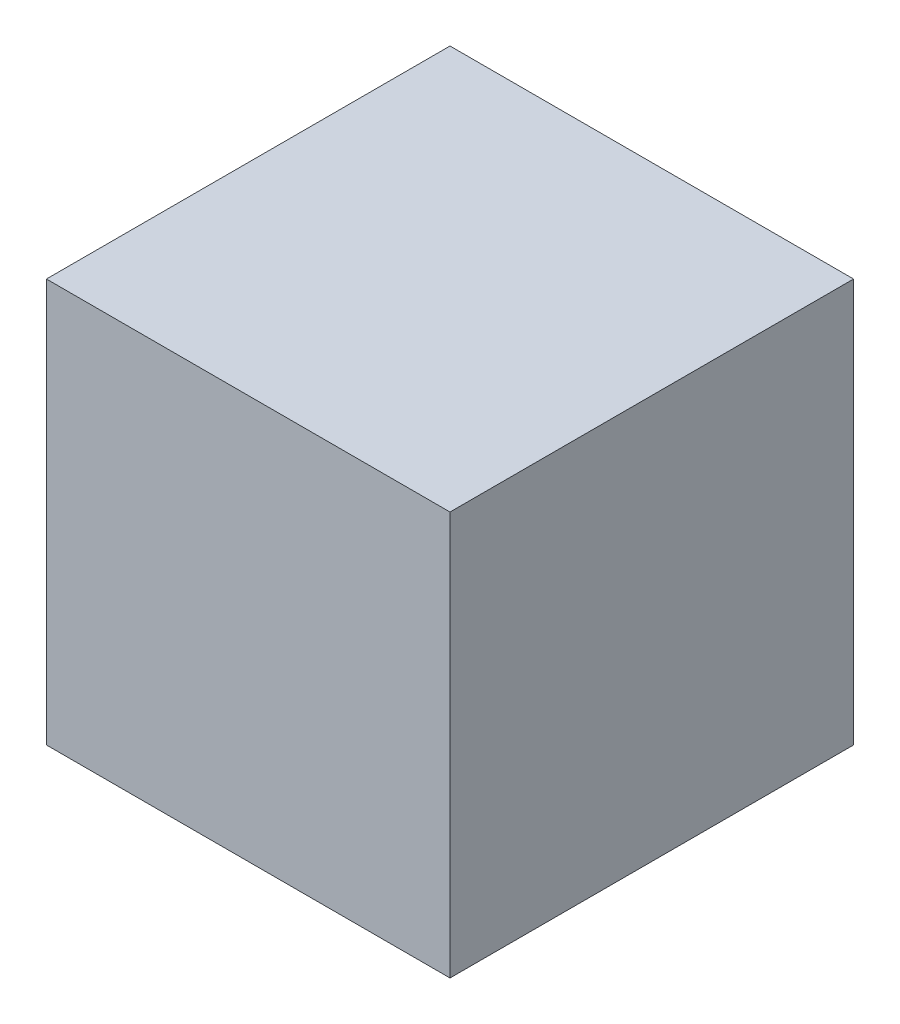
SolidWorks part; units mm, degrees
ref_plane "Front Plane" through (0, 0, 0) normal (0, 0, 1) x (1, 0, 0)
ref_plane "Top Plane" through (0, 0, 0) normal (0, 1, 0) x (1, 0, 0)
ref_plane "Right Plane" through (0, 0, 0) normal (1, 0, 0) x (0, 0, -1)
sketch "Sketch1" plane through (0, 0, 0) normal (0, 1, 0) x (1, 0, 0)
  line L1 (-10, -10) -> (10, -10)
  line L2 (-10, -10) -> (-10, 10)
  line L3 (-10, 10) -> (10, 10)
  line L4 (10, -10) -> (10, 10)
  line L5 (-10, -10) -> (10, 10) construction
  line L6 (-10, 10) -> (10, -10) construction
  point P0 (0, 0)
  dimension "D1" = 20
  dimension "D2" = 20
extrude "Boss-Extrude1" add sketch "Sketch1" along normal blind 10 and the other way blind 10
